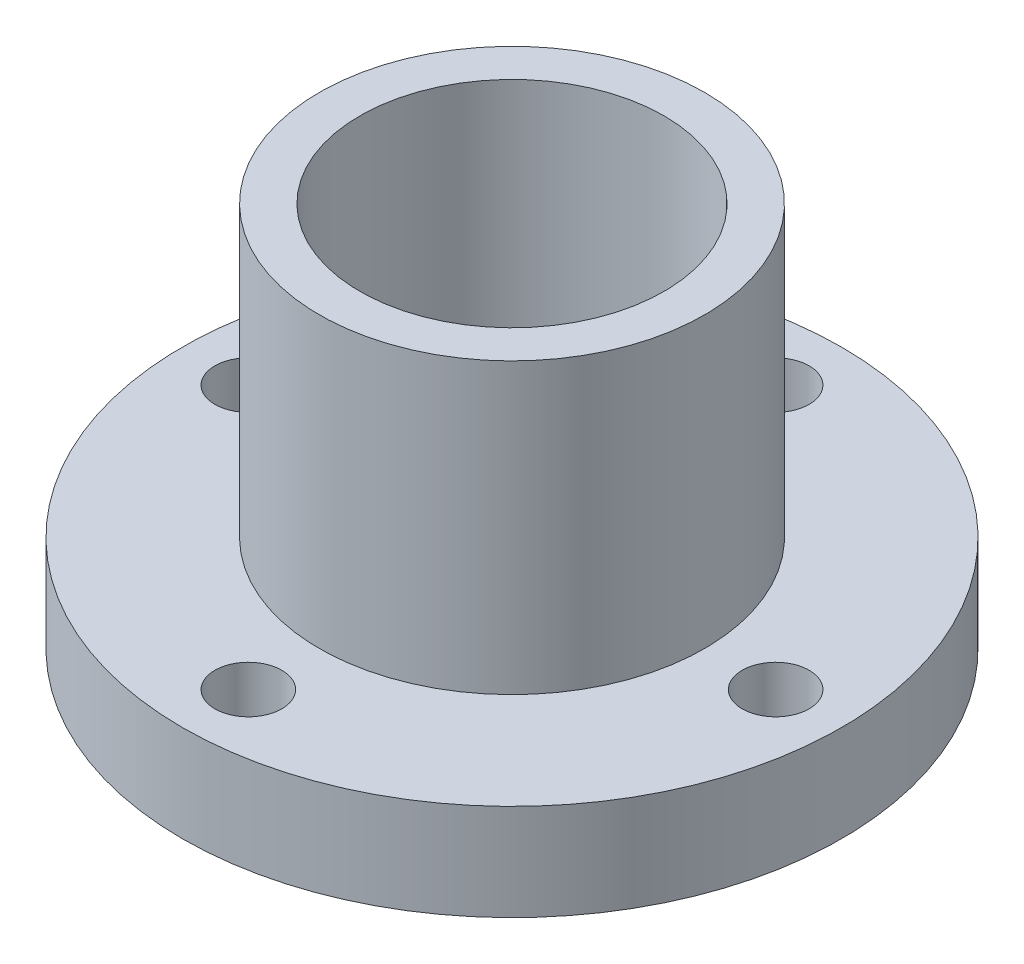
SolidWorks part; units mm, degrees
material "ALUMINIUM,  6082-T6 (HE30TF)"
ref_plane "Front Plane" through (0, 0, 0) normal (0, 0, 1) x (1, 0, 0)
ref_plane "Top Plane" through (0, 0, 0) normal (0, 1, 0) x (1, 0, 0)
ref_plane "Right Plane" through (0, 0, 0) normal (1, 0, 0) x (0, 0, -1)
sketch "Sketch1" plane through (0, 0, 0) normal (0, 0, 1) x (1, 0, 0)
  line L0 (0, 0) -> (0, 38) construction
  line L1 (15, 38) -> (15, 0)
  line L2 (15, 0) -> (32.5, 0)
  line L3 (32.5, 0) -> (32.5, 9.5)
  line L4 (32.5, 9.5) -> (19, 9.5)
  line L5 (19, 9.5) -> (19, 38)
  line L6 (19, 38) -> (15, 38)
  dimension "D1" = 30
  dimension "D2" = 9.5
  dimension "D3" = 38
  dimension "D4" = 65
  dimension "D5" = 38
revolve "Revolve1" add sketch "Sketch1" angle 360 about L0
hole_wizard "Ø6.6 (6.6) Diameter Hole1" positions "Sketch2" profile "Sketch3" hole size "Ø6.6" standard "ISO" end condition through all
sketch "Sketch2" plane through (0, 9.5, 0) normal (0, 1, 0) x (1, 0, 0)
  line L0 (0, 26) -> (0, -26) construction
  line L3 (26, 0) -> (-26, 0) construction
  point P0 (0, 26)
  point P2 (0, -26)
  point P4 (26, 0)
  point P6 (-26, 0)
  dimension "D1" = 52
sketch "Sketch3" plane through (0, 9.5, -26) normal (1, 0, 0) x (0, 0, 1)
  line L0 (0, 0) -> (0, 9.5)
  line L1 (0, 9.5) -> (3.3, 9.5)
  line L2 (3.3, 9.5) -> (3.3, 0)
  line L5 (3.3, 0) -> (0, 0)
  line L11 (0, -6.35) -> (0, 107.95) construction
  dimension "Thru Hole Dia." = 6.6
  dimension "Thru Hole Depth" = 9.5
ref_axis "Axis1" through (0, 38, 0) along (0, -1, 0)
ref_plane "Plane1" through (0, 0, 0) normal (-0.5736, 0, 0.8192) x (0, -1, 0)
sketch "Sketch4" plane through (0, 0, 0) normal (-0.5736, 0, 0.8192) x (0, -1, 0)
  line L0 (-25, 0) -> (0, 0) construction
  circle A0 centre (-25, 0) radius 7.5
  dimension "D1" = 15
  dimension "D2" = 25
extrude "Cut-Extrude1" [suppressed] cut sketch "Sketch4" along normal blind 30
